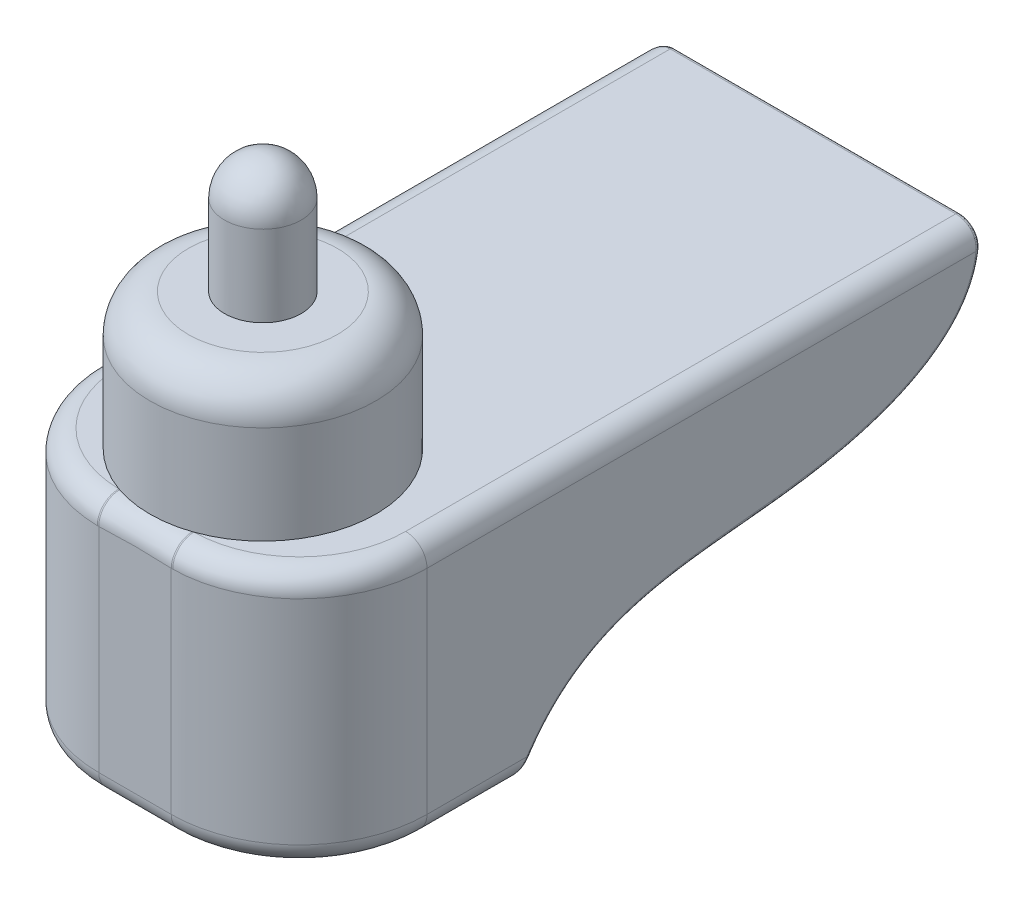
SolidWorks part; units mm, degrees
ref_plane "Front Plane" through (0, 0, 0) normal (0, 0, 1) x (1, 0, 0)
ref_plane "Top Plane" through (0, 0, 0) normal (0, 1, 0) x (1, 0, 0)
ref_plane "Right Plane" through (0, 0, 0) normal (1, 0, 0) x (0, 0, -1)
sketch "Sketch1" plane through (0, 0, 0) normal (1, 0, 0) x (0, 0, -1)
  line L0 (0, 0) -> (0, 60)
  line L1 (0, 60) -> (160, 60)
  line L2 (0, 0) -> (51.5656, 0)
  spline S0 degree 3 poles (160, 60) (161.1255, 42.0823) (114.2919, 18.8873) (67.9238, 30.6859) (51.5656, 0) knots 0 0 0 0 0.356112 1 1 1 1
  dimension "D1" = 160
  dimension "D2" = 60
  dimension "D3" = 30
  dimension "D4" = 40
extrude "Boss-Extrude1" add sketch "Sketch1" along normal blind 77
sketch "Sketch2" plane through (0, 60, 0) normal (0, 1, 0) x (1, 0, 0)
  line L0 (38.5, 160) -> (38.5, 0) construction
  line L1 (77, 160) -> (0, 160) construction
  line L2 (77, 0) -> (0, 0) construction
  circle A0 centre (38.5, 30) radius 26.5
  dimension "D1" = 53
  dimension "D2" = 30
extrude "Boss-Extrude2" add sketch "Sketch2" along normal blind 32
sketch "Sketch3" plane through (0, 92, 0) normal (0, 1, 0) x (1, 0, 0)
  circle A0 centre (38.5, 30) radius 26.5
  circle A1 centre (38.5, 30) radius 26.5 construction
  circle A2 centre (38.5, 30) radius 9
  dimension "D1" = 53
  dimension "D2" = 0
  dimension "D3" = 18
extrude "Boss-Extrude3" add sketch "Sketch3" along normal blind 28 contours A2
fillet "Fillet1" radius 9 1 edges at (38.5, 120, -21)
fillet "Fillet2" radius 9 1 edges at (38.5, 92, -3.5)
fillet "Fillet3" radius 30 2 edges at (0, 30, 0) (77, 30, 0)
fillet "Fillet4" radius 5 10 edges at (77, 60, -95) (68.2132, 60, -8.7868) (8.7868, 60, -8.7868) (77, 0, -40.7828) (68.2132, 0, -8.7868) (38.5, 0, 0) (8.7868, 0, -8.7868) (0, 60, -95) (0, 0, -40.7828)
fillet "Fillet5" radius 1 7 edges at (2.204, 0.8548, -51.0551) (38.5, 0, -51.5656) (75.5602, 1.4893, -52.3871) (75.1215, 58.9059, -160.047) (2.5135, 59.3379, -159.371) (38.5, 60, -160)
